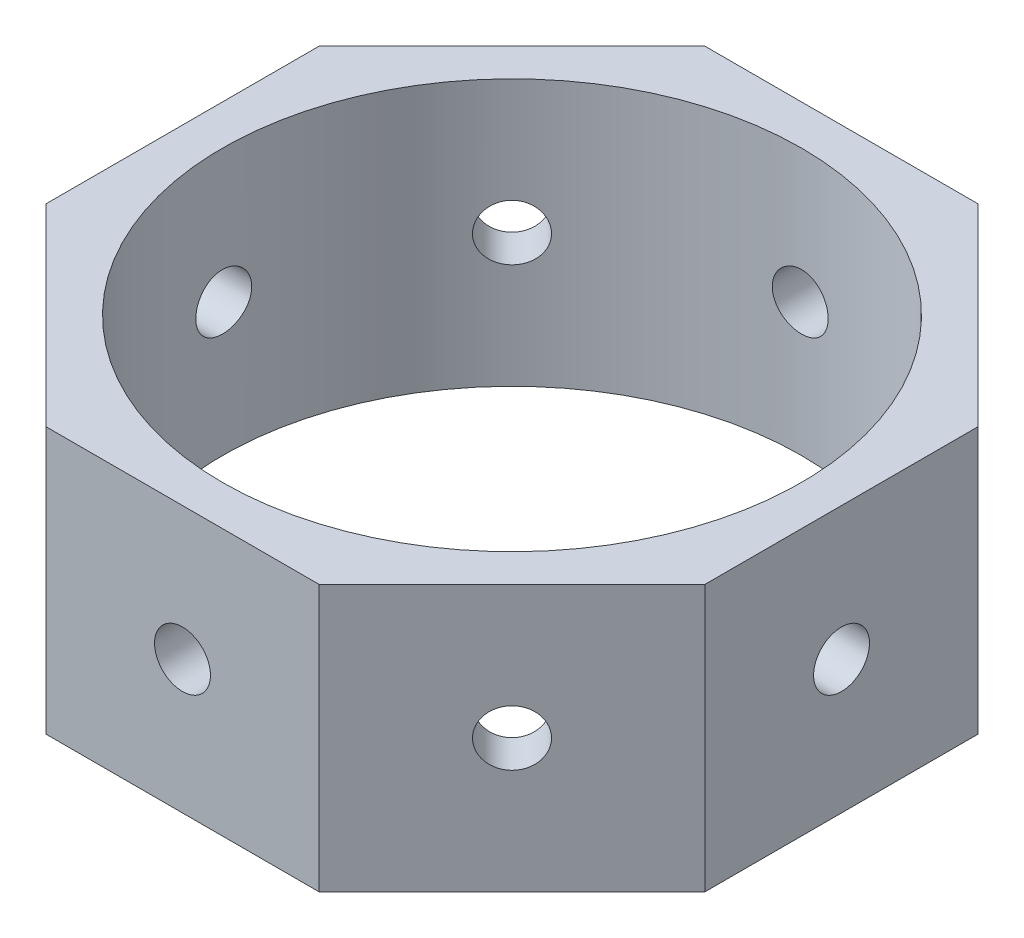
SolidWorks part; units mm, degrees
ref_plane "Front Plane" through (0, 0, 0) normal (0, 0, 1) x (1, 0, 0)
ref_plane "Top Plane" through (0, 0, 0) normal (0, 1, 0) x (1, 0, 0)
ref_plane "Right Plane" through (0, 0, 0) normal (1, 0, 0) x (0, 0, -1)
sketch "Sketch1" plane through (0, 0, 0) normal (0, 1, 0) x (1, 0, 0)
  line L1 (13.0198, 31.4325) -> (-13.0198, 31.4325)
  line L2 (-13.0198, 31.4325) -> (-31.4325, 13.0198)
  line L3 (-31.4325, 13.0198) -> (-31.4325, -13.0198)
  line L4 (-31.4325, -13.0198) -> (-13.0198, -31.4325)
  line L5 (-13.0198, -31.4325) -> (13.0198, -31.4325)
  line L6 (13.0198, -31.4325) -> (31.4325, -13.0198)
  line L7 (31.4325, -13.0198) -> (31.4325, 13.0198)
  line L8 (31.4325, 13.0198) -> (13.0198, 31.4325)
  line L9 (0, 31.4325) -> (0, 0) construction
  circle A1 centre (0, 0) radius 27.6225
  circle A2 centre (0, 0) radius 31.4325 construction
  point P3 (0, 0)
  point P5 (0, 27.6225)
  point P8 (0, 0)
  dimension "D1" = 55.245
  dimension "D2" = 3.81
  dimension "D3" = 62.865
extrude "Boss-Extrude1" add sketch "Sketch1" along normal blind 25.4
sketch "Sketch2" plane through (0, 0, 31.4325) normal (0, 0, 1) x (1, 0, 0)
  line L0 (0, 0) -> (0, 25.4) construction
  line L1 (-13.0198, 25.4) -> (13.0198, 25.4) construction
  line L2 (-13.0198, 0) -> (13.0198, 0) construction
  circle A0 centre (0, 12.7) radius 2.667
  dimension "D1" = 5.334
  dimension "D2" = 12.7
extrude "Cut-Extrude1" cut sketch "Sketch2" against normal up to next
pattern_circular "CirPattern1" count 8 over 360 about axis through (0, 25.4, 0) along (0, 1, 0) of "Cut-Extrude1"
